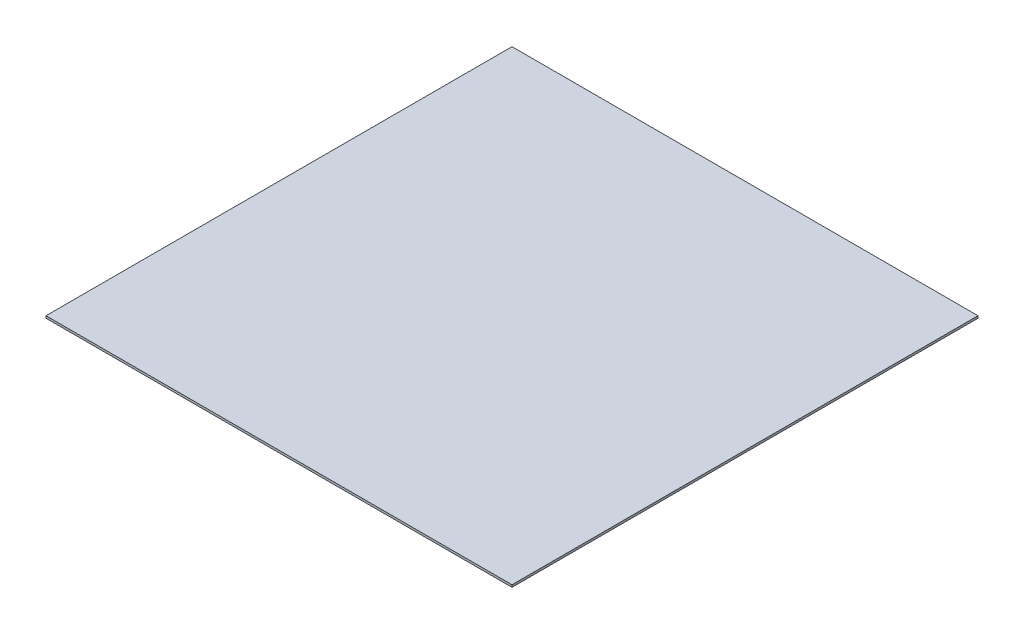
SolidWorks part; units mm, degrees
material "6061-T6 (SS)"
ref_plane "Front Plane" through (0, 0, 0) normal (0, 0, 1) x (1, 0, 0)
ref_plane "Top Plane" through (0, 0, 0) normal (0, 1, 0) x (1, 0, 0)
ref_plane "Right Plane" through (0, 0, 0) normal (1, 0, 0) x (0, 0, -1)
sketch "Sketch1" plane through (0, 0, 0) normal (0, 1, 0) x (1, 0, 0)
  line L1 (0, 0) -> (2000, 0)
  line L2 (0, 0) -> (0, -2000)
  line L3 (0, -2000) -> (2000, -2000)
  line L4 (2000, 0) -> (2000, -2000)
  dimension "D1" = 2000
  dimension "D2" = 2000
extrude "Boss-Extrude1" add sketch "Sketch1" along normal blind 9.525
sketch "Sketch2" plane through (0, 0, 2000) normal (0, 0, 1) x (1, 0, 0)
  line L0 (1000, 0) -> (1000, 9.525) construction
  line L1 (0, 0) -> (2000, 0) construction
  line L2 (0, 9.525) -> (2000, 9.525) construction
sketch "Sketch3" plane through (0, 0, 0) normal (0, -1, 0) x (1, 0, 0)
  line L0 (1000, 2000) -> (1000, 1850) construction
  line L1 (0, 2000) -> (2000, 2000) construction
  dimension "D1" = 150
